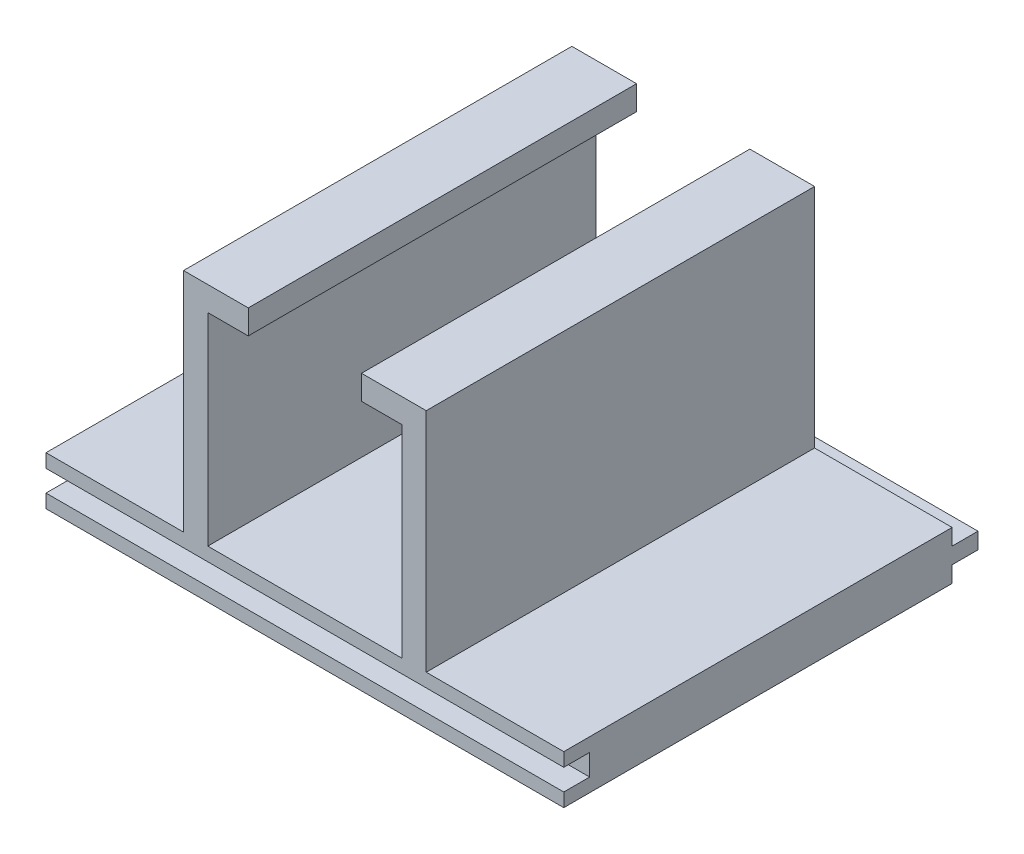
SolidWorks part; units mm, degrees
ref_plane "Front Plane" through (0, 0, 0) normal (0, 0, 1) x (1, 0, 0)
ref_plane "Top Plane" through (0, 0, 0) normal (0, 1, 0) x (1, 0, 0)
ref_plane "Right Plane" through (0, 0, 0) normal (1, 0, 0) x (0, 0, -1)
sketch "Sketch1" plane through (0, 0, 0) normal (0, 1, 0) x (1, 0, 0)
  line L1 (0, 0) -> (101.6, 0)
  line L2 (0, 0) -> (0, 76.2)
  line L3 (0, 76.2) -> (101.6, 76.2)
  line L4 (101.6, 0) -> (101.6, 76.2)
  dimension "D1" = 101.6
  dimension "D2" = 76.2
extrude "Boss-Extrude1" add sketch "Sketch1" along normal blind 9.525
sketch "Sketch2" plane through (0, 9.525, 0) normal (0, 1, 0) x (1, 0, 0)
  line L0 (0, 0) -> (101.6, 0) construction
  line L5 (26.9875, 0) -> (31.75, 0)
  line L6 (26.9875, 0) -> (26.9875, 76.2)
  line L7 (26.9875, 76.2) -> (31.75, 76.2)
  line L8 (31.75, 0) -> (31.75, 76.2)
  line L9 (101.6, 76.2) -> (0, 76.2) construction
  point P8 (50.8, 0)
  dimension "D1" = 19.05
  dimension "D2" = 4.7625
extrude "Boss-Extrude2" add sketch "Sketch2" along normal blind 44.45
sketch "Sketch3" plane through (31.75, 0, 0) normal (1, 0, 0) x (0, 0, -1)
  line L0 (76.2, 53.975) -> (76.2, 9.525) construction
  line L1 (0, 53.975) -> (76.2, 53.975)
  line L2 (0, 53.975) -> (0, 49.2125)
  line L3 (0, 49.2125) -> (76.2, 49.2125)
  line L4 (76.2, 53.975) -> (76.2, 49.2125)
  dimension "D1" = 4.7625
extrude "Boss-Extrude3" add sketch "Sketch3" along normal blind 7.9375
ref_plane "Plane1" through (50.8, 0, 0) normal (1, 0, 0) x (0, 0, -1)
sketch "Sketch5" plane through (0, 0, 0) normal (0, 0, 1) x (1, 0, 0)
  line L0 (101.6, 9.525) -> (101.6, 0) construction
  line L1 (101.6, 2.667) -> (0, 2.667)
  line L2 (101.6, 2.667) -> (101.6, 6.858)
  line L3 (101.6, 6.858) -> (0, 6.858)
  line L4 (0, 2.667) -> (0, 6.858)
  line L5 (0, 9.525) -> (0, 0) construction
  dimension "D1" = 2.667
  dimension "D2" = 4.191
extrude "Cut-Extrude1" cut sketch "Sketch5" against normal blind 5.08
sketch "Sketch6" plane through (0, 0, -76.2) normal (0, 0, -1) x (-1, 0, 0)
  line L0 (-101.6, 9.525) -> (-101.6, 0) construction
  line L1 (-101.6, 6.35) -> (0, 6.35)
  line L2 (-101.6, 6.35) -> (-101.6, 3.175)
  line L3 (-101.6, 3.175) -> (0, 3.175)
  line L4 (0, 6.35) -> (0, 3.175)
  line L5 (0, 9.525) -> (0, 0) construction
  dimension "D1" = 3.175
  dimension "D2" = 3.175
extrude "Boss-Extrude5" add sketch "Sketch6" along normal blind 5.08
mirror "Mirror1" about plane through (50.8, 0, 0) normal (1, 0, 0) of "Boss-Extrude3", "Boss-Extrude2"
